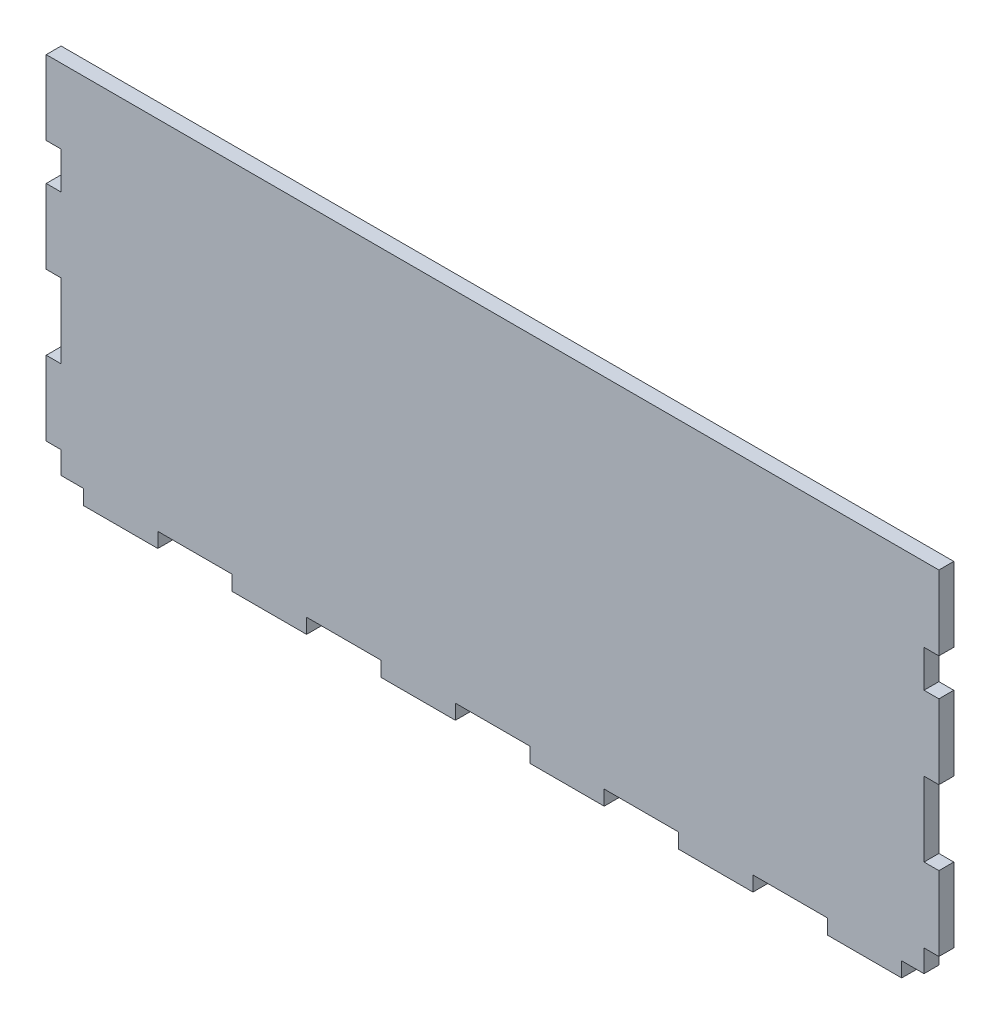
SolidWorks part; units mm, degrees
ref_plane "Front Plane" through (0, 0, 0) normal (0, 0, 1) x (1, 0, 0)
ref_plane "Top Plane" through (0, 0, 0) normal (0, 1, 0) x (1, 0, 0)
ref_plane "Right Plane" through (0, 0, 0) normal (1, 0, 0) x (0, 0, -1)
sketch "Sketch1" plane through (0, 0, 0) normal (0, 0, 1) x (1, 0, 0)
  line L0 (0, 0) -> (0, -127) construction
  line L1 (152.4, 0) -> (-152.4, 0)
  line L2 (12.7, -127) -> (-12.7, -127)
  line L3 (-12.7, -127) -> (-12.7, -121.92)
  line L4 (-12.7, -121.92) -> (-38.1, -121.92)
  line L5 (-38.1, -121.92) -> (-38.1, -127)
  line L6 (-38.1, -127) -> (-63.5, -127)
  line L7 (-63.5, -127) -> (-63.5, -121.92)
  line L8 (-63.5, -121.92) -> (-88.9, -121.92)
  line L9 (-88.9, -121.92) -> (-88.9, -127)
  line L10 (-88.9, -127) -> (-114.3, -127)
  line L11 (-152.4, -127) -> (-152.4, -114.3)
  line L12 (-114.3, -127) -> (-114.3, -121.92)
  line L13 (-114.3, -121.92) -> (-139.7, -121.92)
  line L14 (-139.7, -121.92) -> (-139.7, -127)
  line L15 (-139.7, -127) -> (-152.4, -127)
  line L16 (-152.4, -114.3) -> (-147.32, -114.3)
  line L17 (-147.32, -114.3) -> (-147.32, -88.9)
  line L18 (-147.32, -88.9) -> (-152.4, -88.9)
  line L19 (-152.4, -63.5) -> (-147.32, -63.5)
  line L20 (-147.32, -63.5) -> (-147.32, -38.1)
  line L21 (-147.32, -38.1) -> (-152.4, -38.1)
  line L22 (-152.4, -25.4) -> (-147.32, -25.4)
  line L23 (-147.32, -25.4) -> (-147.32, 0)
  line L24 (-152.4, -88.9) -> (-152.4, -63.5)
  line L25 (-152.4, -38.1) -> (-152.4, -25.4)
  line L26 (152.4, -38.1) -> (152.4, -25.4)
  line L27 (152.4, -88.9) -> (152.4, -63.5)
  line L28 (147.32, -25.4) -> (147.32, 0)
  line L29 (152.4, -25.4) -> (147.32, -25.4)
  line L30 (147.32, -38.1) -> (152.4, -38.1)
  line L31 (147.32, -63.5) -> (147.32, -38.1)
  line L32 (152.4, -63.5) -> (147.32, -63.5)
  line L33 (147.32, -88.9) -> (152.4, -88.9)
  line L34 (147.32, -114.3) -> (147.32, -88.9)
  line L35 (152.4, -114.3) -> (147.32, -114.3)
  line L36 (139.7, -127) -> (152.4, -127)
  line L37 (139.7, -121.92) -> (139.7, -127)
  line L38 (114.3, -121.92) -> (139.7, -121.92)
  line L39 (114.3, -127) -> (114.3, -121.92)
  line L40 (152.4, -127) -> (152.4, -114.3)
  line L41 (88.9, -127) -> (114.3, -127)
  line L42 (88.9, -121.92) -> (88.9, -127)
  line L43 (63.5, -121.92) -> (88.9, -121.92)
  line L44 (63.5, -127) -> (63.5, -121.92)
  line L45 (38.1, -127) -> (63.5, -127)
  line L46 (38.1, -121.92) -> (38.1, -127)
  line L47 (12.7, -121.92) -> (38.1, -121.92)
  line L48 (12.7, -127) -> (12.7, -121.92)
  line L49 (-147.32, 0) -> (147.32, 0)
  line L50 (-152.4, 0) -> (-152.4, -127)
  line L51 (-152.4, -127) -> (152.4, -127)
  line L52 (152.4, -127) -> (152.4, 0)
  line L53 (-147.32, 0) -> (-147.32, -114.3)
  line L54 (-139.7, -121.92) -> (139.7, -121.92)
  line L55 (147.32, 0) -> (147.32, -114.3)
  line L56 (-139.7, -121.92) -> (-152.4, -121.92)
  line L57 (139.7, -121.92) -> (152.4, -121.92)
  line L58 (-147.32, -114.3) -> (-147.32, -121.92)
  line L59 (147.32, -114.3) -> (147.32, -121.92)
  dimension "D1" = 152.4
  dimension "D2" = 127
  dimension "D3" = 12.7
  dimension "D4" = 25.4
  dimension "D5" = 5.08
  dimension "D6" = 12.7
  dimension "D7" = 25.4
extrude "Boss-Extrude1" add sketch "Sketch1" along normal mid plane 5.08 contours L1 L50 L22 L23 | L21 L50 L19 L20 | L18 L50 L16 L17 | L14 L51 L12 L13 | L9 L51 L7 L8 | L0 L49 L23 L53 L20 L17 L16 L11 L15 L14 L13 L54 L8 L4 | L1 L0 L54 L47 L43 L38 L37 L36 L40 L35 L34 L55 L31 L28 | L5 L51 L3 L4 | L44 L51 L42 L43 | L48 L51 L46 L47 | L39 L51 L37 L38 | L35 L52 L33 L34 | L32 L52 L30 L31 | L29 L52 L1 L28 region at (73.66, -60.96, 0) region at (-73.66, -60.96, 0) region at (149.86, -12.7, 0) region at (-149.86, -12.7, 0) region at (-25.4, -124.46, 0) region at (25.4, -124.46, 0) region at (149.86, -50.8, 0) region at (-149.86, -50.8, 0) region at (-76.2, -124.46, 0) region at (76.2, -124.46, 0) region at (149.86, -101.6, 0) region at (-149.86, -101.6, 0) region at (-127, -124.46, 0) region at (127, -124.46, 0)
